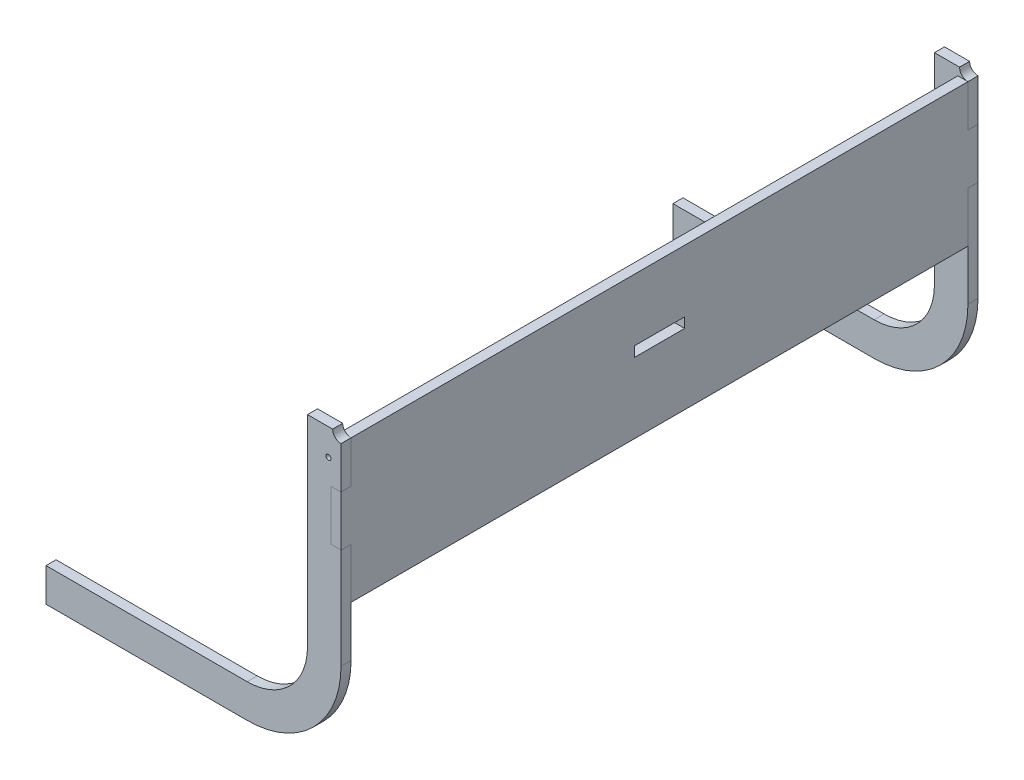
SolidWorks part; units mm, degrees
note: The reader was unsure of these and kept them because the rebuilt part matched: shared geometry of "Sketch1<2>".
material "Teak"
ref_plane "Front Plane" through (0, 0, 0) normal (0, 0, 1) x (1, 0, 0)
ref_plane "Top Plane" through (0, 0, 0) normal (0, 1, 0) x (1, 0, 0)
ref_plane "Right Plane" through (0, 0, 0) normal (1, 0, 0) x (0, 0, -1)
sketch "Sketch1" plane through (0, 0, 196) normal (0, 0, 1) x (1, 0, 0)
  line L0 (91, -68) -> (31, -68)
  line L1 (23, -60) -> (23, 0)
  line L2 (91, -88) -> (91, -68)
  line L3 (3, 0) -> (23, 0)
  line L6 (31, -91) -> (91, -91)
  line L7 (91, -91) -> (91, -88)
  line L8 (91, -88) -> (31, -88)
  line L9 (3, -60) -> (3, 0)
  line L10 (3, 0) -> (0, 0)
  line L11 (0, 0) -> (0, -60)
  line L14 (91, -88) -> (31, -88)
  line L15 (3, -60) -> (3, 0)
  arc A0 (23, -60) -> (31, -68) centre (31, -60) ccw
  arc A2 (3, -60) -> (31, -88) centre (31, -60) ccw
  arc A3 (0, -60) -> (31, -91) centre (31, -60) ccw
  arc A4 (3, -60) -> (31, -88) centre (31, -60) ccw
  dimension "D1" = 0
  dimension "D2" = 20
extrude "Boss-Extrude1" add sketch "Sketch1" against normal blind 3
extrude "Boss-Extrude2" add sketch "Sketch1<2>" along normal blind 3 from surface separate body
sketch "Sketch1<2>" plane through (0, 0, 196) normal (0, 0, 1) x (1, 0, 0) same geometry as "Sketch1"
sketch "Sketch2" plane through (0, 0, 196) normal (0, 0, 1) x (1, 0, 0)
  line L0 (3, 0) -> (3, -60) construction
  line L1 (3, -15) -> (6, -15)
  line L2 (3, -15) -> (3, -30)
  line L3 (3, -30) -> (6, -30)
  line L4 (6, -15) -> (6, -30)
  line L5 (23, 0) -> (3, 0) construction
  dimension "D1" = 15
  dimension "D2" = 3
  dimension "D3" = 15
extrude "Cut-Extrude1" cut sketch "Sketch2" against normal through all both and the other way through all
sketch "Sketch3" plane through (3, 0, 0) normal (-1, 0, 0) x (0, 0, 1)
  line L0 (193, -30) -> (193, -60) construction
  line L1 (196, 0) -> (193, 0)
  line L2 (196, 0) -> (196, -15)
  line L3 (196, -15) -> (193, -15)
  line L4 (193, 0) -> (193, -15)
  line L5 (196, -15) -> (193, -15)
  line L6 (196, -15) -> (196, -30)
  line L7 (196, -30) -> (193, -30)
  line L8 (193, -15) -> (193, -30)
  line L9 (196, -30) -> (193, -30)
  line L10 (196, -30) -> (196, -45)
  line L11 (196, -45) -> (193, -45)
  line L12 (193, -30) -> (193, -45)
  line L13 (9, -30) -> (9, -60) construction
  line L14 (193, 0) -> (9, 0)
  line L15 (193, 0) -> (193, -45)
  line L16 (193, -45) -> (9, -45)
  line L17 (9, 0) -> (9, -45)
  line L19 (9, 0) -> (6, 0)
  line L20 (9, 0) -> (9, -15)
  line L21 (9, -15) -> (6, -15)
  line L22 (6, 0) -> (6, -15)
  line L23 (9, -15) -> (6, -15)
  line L24 (9, -15) -> (9, -30)
  line L25 (9, -30) -> (6, -30)
  line L26 (6, -15) -> (6, -30)
  line L27 (9, -30) -> (6, -30)
  line L28 (9, -30) -> (9, -45)
  line L29 (9, -45) -> (6, -45)
  line L30 (6, -30) -> (6, -45)
  line M4 (193, -15) -> (196, -15)
  line M7 (193, 0) -> (193, -15)
  dimension "D1" = 15
extrude "Boss-Extrude3" add sketch "Sketch3" against normal blind 3 separate body contours L14 L17 L16 L12 L8 M7 | L21 L26 L25 L17 | L8 L7 L6 M4
mirror "Mirror1" about plane through (91, -88, 193) normal (1, 0, 0) of bodies 105 103 104
delete or keep bodies "Body-Delete/Keep 1" type delete bodies bodies 105 103 104
sketch "Sketch6" plane through (0, 0, 196) normal (0, 0, 1) x (1, 0, 0)
  circle A0 centre (179, 0) radius 2.5
  dimension "D1" = 5
extrude "Cut-Extrude2" cut sketch "Sketch6" against normal through all both and the other way through all
sketch "Sketch7" plane through (179, 0, 0) normal (1, 0, 0) x (0, 0, -1)
  line L1 (-193, -2.5) -> (-9, -2.5)
  line L2 (-193, -2.5) -> (-193, 0)
  line L3 (-193, 0) -> (-9, 0)
  line L4 (-9, -2.5) -> (-9, 0)
extrude "Cut-Extrude3" cut sketch "Sketch7" against normal through all both and the other way through all
sketch "Sketch8" plane through (176, 0, 0) normal (-1, 0, 0) x (0, 0, 1)
  line L0 (193, -2.5) -> (9, -2.5) construction
  line L1 (108.5, -21) -> (93.5, -21)
  line L2 (108.5, -21) -> (108.5, -24)
  line L3 (108.5, -24) -> (93.5, -24)
  line L4 (93.5, -21) -> (93.5, -24)
  line L5 (9, -15) -> (9, -30) construction
  point P4 (101, -21)
  point P7 (101, -2.5)
  point P10 (9, -22.5)
  point P11 (93.5, -22.5)
  dimension "D1" = 15
  dimension "D2" = 3
extrude "Cut-Extrude4" cut sketch "Sketch8" against normal through all both and the other way through all
sketch "Sketch11" plane through (0, 0, 196) normal (0, 0, 1) x (1, 0, 0)
  line L0 (91, -68) -> (151, -68) construction
  line L1 (159, -60) -> (159, 0) construction
  line L2 (91, -68) -> (151, -68)
  line L3 (159, -60) -> (159, 0)
  line L4 (91, -78) -> (151, -78)
  line L5 (169, -60) -> (169, 0)
  line L6 (91, -68) -> (91, -78)
  line L7 (159, 0) -> (169, 0)
  arc A0 (151, -68) -> (159, -60) centre (151, -60) ccw construction
  arc A1 (151, -68) -> (159, -60) centre (151, -60) ccw
  arc A2 (151, -78) -> (169, -60) centre (151, -60) ccw
  dimension "D1" = 10
extrude "Cut-Extrude6" cut sketch "Sketch11" against normal through all both and the other way through all
sketch "Sketch12" plane through (0, 0, 6) normal (0, 0, -1) x (-1, 0, 0)
  line L0 (-179, 0) -> (-175.25, -7.9057) construction
  line L1 (-176, -21) -> (-176, -24) construction
  circle A0 centre (-175.25, -7.9057) radius 0.75
  dimension "D2" = 1.5
  dimension "D1" = 8.75
extrude "Cut-Extrude7" cut sketch "Sketch12" against normal through all both and the other way through all
